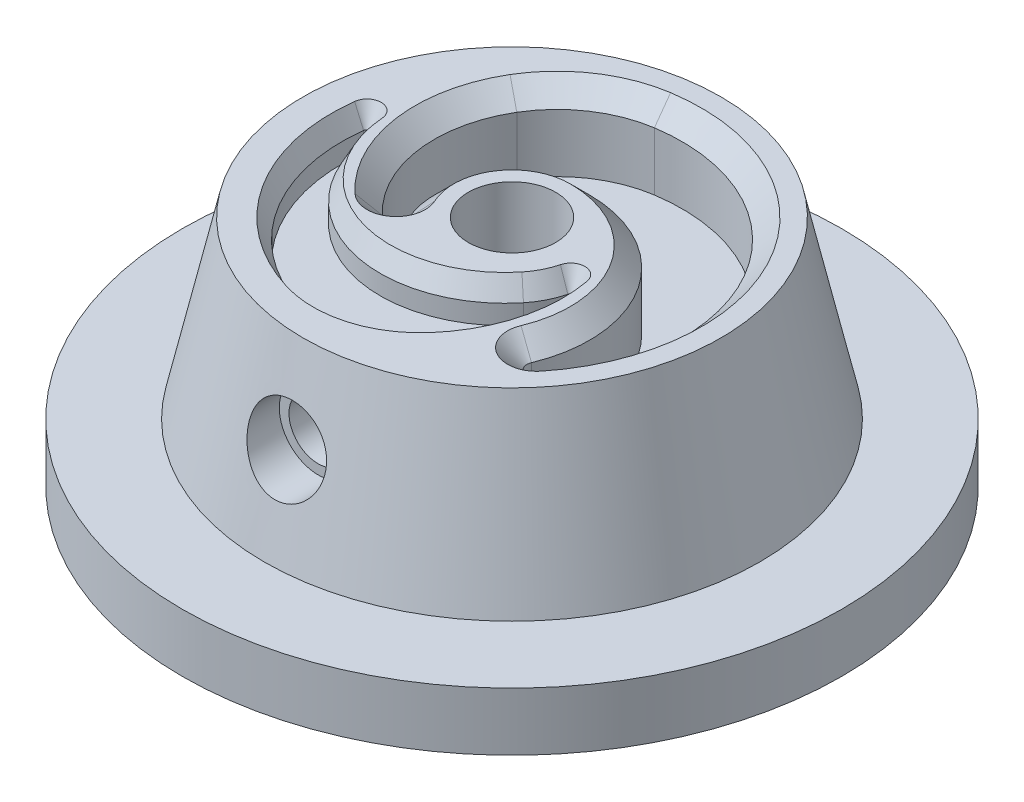
SolidWorks part; units mm, degrees
ref_plane "Front Plane" through (0, 0, 0) normal (0, 0, 1) x (1, 0, 0)
ref_plane "Top Plane" through (0, 0, 0) normal (0, 1, 0) x (1, 0, 0)
ref_plane "Right Plane" through (0, 0, 0) normal (1, 0, 0) x (0, 0, -1)
sketch "Sketch1" plane through (0, 0, 0) normal (0, 1, 0) x (1, 0, 0)
  circle A0 centre (0, 0) radius 13
  dimension "D1" = 26
extrude "Boss-Extrude1" add sketch "Sketch1" along normal blind 10
sketch "Sketch2" plane through (0, 0, 0) normal (1, 0, 0) x (0, 0, -1)
  line L0 (-13, 0) -> (-10.7714, 10)
  line L1 (13, 10) -> (-13, 10) construction
  line L2 (-10.7714, 10) -> (-13, 10)
  line L3 (-13, 10) -> (-13, 0)
  line L4 (0, 0) -> (0, 50000) construction
  line L5 (-13, 0) -> (13, 0) construction
  point P11 (0, 0)
  dimension "D1" = 12.563
revolve "Cut-Revolve1" cut sketch "Sketch2" angle 360 about L4
sketch "Sketch3" plane through (0, 0, 0) normal (0, -1, 0) x (-1, 0, 0)
  circle A0 centre (0, 0) radius 17
  dimension "D1" = 34
extrude "Boss-Extrude2" add sketch "Sketch3" along normal blind 2
sketch "Sketch4" [suppressed] plane through (0, -2, 0) normal (0, -1, 0) x (1, 0, 0)
  line L0 (1.145, -2.3899) -> (1.145, 2.3899)
  line L1 (-1.145, -2.3899) -> (-1.145, 2.3899)
  line L2 (0, 0) -> (35355.3391, 35355.3391) construction
  line L3 (0.8543, 0) -> (50000.8543, 0) construction
  line L4 (-2.3899, 1.145) -> (2.3899, 1.145)
  line L5 (-2.3899, -1.145) -> (2.3899, -1.145)
  circle A0 centre (0, 0) radius 2.65
  dimension "D1" = 5.3
  dimension "D2" = 2.29
  dimension "D3" = 45
extrude "Cut-Extrude1" [suppressed] cut sketch "Sketch4" against normal through all contours L1 L5 L0 L4 | L4 A0 L5 L1 | L0 A0 L1 L4 | L5 A0 L4 L0 | L1 A0 L0 L5
fillet "Fillet1" [suppressed] radius 0.5
sketch "Sketch5" plane through (0, 10, 0) normal (0, 1, 0) x (1, 0, 0)
  line L0 (-1.6771, 1.5) -> (1.6771, 1.5)
  circle A0 centre (0, 0) radius 2.25
  dimension "D1" = 4.5
  dimension "D2" = 1.5
extrude "4-mm shaft hole" cut sketch "Sketch5" against normal through all contours L0 A0 | A0 region at (0, 10, 0.222)
ref_plane "Plane1" through (0, 2.7601, 12.3849) normal (0, 0.2175, 0.9761) x (1, 0, 0)
sketch "Sketch7" [suppressed] plane through (0, 10, 0) normal (0, 1, 0) x (1, 0, 0)
  circle A0 centre (0, -9.7714) radius 1.6
  circle A1 centre (0, 0) radius 9.7714 construction
  circle A2 centre (0, 0) radius 10.7714 construction
  dimension "D1" = 3.2
  dimension "D2" = 1
sketch "Sketch8" [suppressed] plane through (0, 0, 0) normal (0, 1, 0) x (1, 0, 0)
  circle A0 centre (0, -12) radius 1.6
  circle A1 centre (0, 0) radius 12 construction
  circle A2 centre (0, 0) radius 13 construction
  circle A4 centre (0, -9.7714) radius 1.6 construction
  dimension "D1" = 1
loft "Cut-Loft1" [suppressed] cut profiles "Sketch7", "Sketch8"
pattern_circular "CirPattern1" [suppressed] count 15 over 360 of bodies 106
fillet "Fillet2" [suppressed] radius 0.3
sketch "Sketch9" plane through (0, 0, 0) normal (0, 1, 0) x (1, 0, 0)
  circle A0 centre (0, 0) radius 17
  circle A1 centre (0, 0) radius 17 construction
  circle A2 centre (0, 0) radius 2.25
  circle A3 centre (0, 0) radius 2.25 construction
extrude "Boss-Extrude3" add sketch "Sketch9" along normal blind 1
sketch "Sketch10" plane through (0, 0, 0) normal (0, 0, 1) x (1, 0, 0)
  line L0 (0, 1) -> (0, 10) construction
  line L1 (17, 1) -> (-17, 1) construction
  line L2 (10.7714, 10) -> (-10.7714, 10) construction
  line L3 (2.25, 10) -> (-2.25, 10) construction
  circle A0 centre (0, 5.5) radius 1.5
  circle A1 centre (0, 5.5) radius 2
  dimension "D1" = 3
  dimension "D2" = 4
extrude "Cut-Extrude3" cut sketch "Sketch10" along normal through all contours L0 A0 | A0 L0 region at (-0.6366, 5.5, 0) region at (0.6366, 5.5, 0)
extrude "Cut-Extrude4" cut sketch "Sketch10<3>" along normal through all from offset 10
sketch "Sketch10<3>" plane through (0, 0, 0) normal (0, 0, 1) x (1, 0, 0) same geometry as "Sketch10"
sketch "Sketch11" plane through (0, 10, 0) normal (0, 1, 0) x (1, 0, 0)
  line L0 (0, 4) -> (6.5318, 4) construction
  line L1 (0, -4) -> (14.8517, -4) construction
  circle A0 centre (0, 0) radius 8.7714
  circle A1 centre (0, 0) radius 4
  circle A2 centre (0, 0) radius 10.7714 construction
  arc A3 (0, 4) -> (3, -8.2424) centre (0, -2.4888) cw
  circle A4 centre (0, 0) radius 12.0922 construction
  arc A6 (0, -4) -> (-3, 8.2424) centre (0, 2.4888) cw
  point P17 (0, -4)
  point P19 (-2.9924, 8.2452)
  point P20 (0, -4)
  point P21 (0, 0)
  dimension "D1" = 8
  dimension "D2" = 2
  dimension "D3" = 3
  dimension "D4" = 3
extrude "Cut-Extrude5" cut sketch "Sketch11" against normal blind 4 contours A6 A1 A3 A0 region at (6.9979, 10, 4.9)
fillet "Fillet3" radius 6 1 edges at (-3, 8, -8.2424)
fillet "Fillet4" radius 0.5 2 edges at (3, 8, 8.2424) (0, 8.5, 4)
chamfer "Chamfer1" distance 1 angle 45 7 edges at (-3.3712, 10, -2.1529) (5.399, 10, -1.1106) (-3.789, 10, 2.2976) (6.1961, 10, 5.6067) (-6.4243, 10, -1.5762) (7.5977, 10, -4.3833) (-3.7685, 10, -7.7179)
sketch "Sketch14" plane through (0, 10, 0) normal (0, 1, 0) x (1, 0, 0)
  line L0 (-7.9496, 3.707) -> (-6.7428, 6.2949) construction
  line L1 (-7.9496, 3.707) -> (0, 0) construction
  line L2 (1.7352, 0) -> (50001.7352, 0) construction
  line L3 (3.1086, -2.5173) -> (7.3631, 2.7365) construction
  circle A0 centre (0, 0) radius 8.7714
  circle A1 centre (0, 0) radius 10.7714 construction
  circle A2 centre (0, 0) radius 4
  arc A3 (4, 0) -> (0, -8.7714) centre (-2.6184, -2.2796) cw
  arc A7 (3.1086, -2.5173) -> (-7.9496, 3.707) centre (-1.8927, 1.5326) cw
  point P11 (7.8175, -0.7682)
  dimension "D1" = 2
  dimension "D2" = 8
  dimension "D3" = 7
  dimension "D5" = 25
  dimension "D6" = 51
extrude "Cut-Extrude7" cut sketch "Sketch14" against normal blind 2 contours A2 A7 A0 A3 region at (-1.8928, 10, 5.2059)
fillet "Fillet6" radius 5 1 edges at (0, 9, 8.7714)
fillet "Fillet8" radius 0.2 2 edges at (-7.9496, 9, -3.707) (4, 9, 0)
chamfer "Chamfer3" distance 1 angle 28 7 edges at (-3.8101, 10, 4.6105) (-8.5046, 10, -1.2316) (3.5737, 10, 1.7969) (-7.3628, 10, 4.7673) (4.0751, 10, 0.8436) (0.2337, 10, 8.4158) (4.1284, 10, 4.1453) first distance on face at (-3.2053, 9, 2.6729) first distance on face at (-8.5066, 9, -1.1414) first distance on face at (3.5326, 9, 1.7762) first distance on face at (-6.5083, 9, 4.214) first distance on face at (4.0724, 9, 0.9221) first distance on face at (0.1252, 9, 8.0291) first distance on face at (3.7887, 9, 4.0514)
